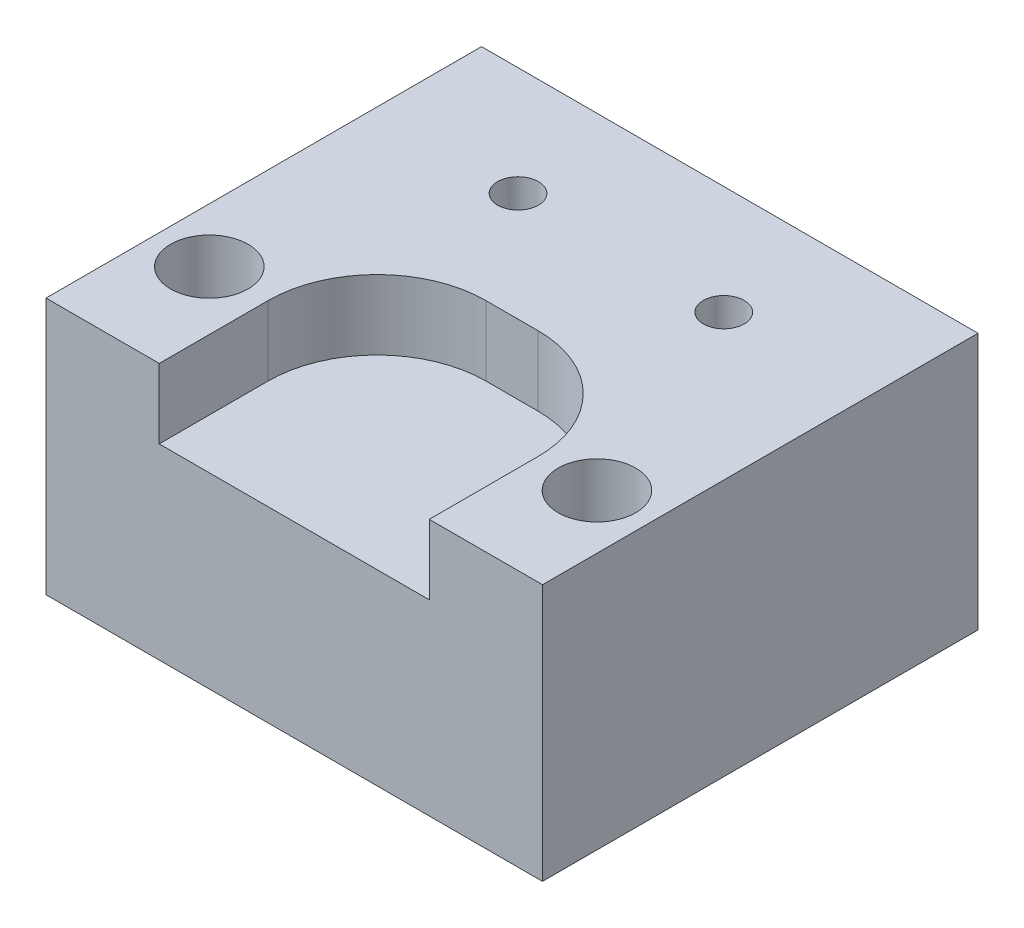
SolidWorks part; units mm, degrees
ref_plane "Front Plane" through (0, 0, 0) normal (0, 0, 1) x (1, 0, 0)
ref_plane "Top Plane" through (0, 0, 0) normal (0, 1, 0) x (1, 0, 0)
ref_plane "Right Plane" through (0, 0, 0) normal (1, 0, 0) x (0, 0, -1)
sketch "Sketch1" plane through (0, 0, 0) normal (0, 1, 0) x (1, 0, 0)
  line L1 (-7.239, -6.35) -> (7.239, -6.35)
  line L2 (-7.239, -6.35) -> (-7.239, 6.35)
  line L3 (-7.239, 6.35) -> (7.239, 6.35)
  line L4 (7.239, -6.35) -> (7.239, 6.35)
  line L5 (-7.239, -6.35) -> (7.239, 6.35) construction
  line L6 (-7.239, 6.35) -> (7.239, -6.35) construction
  point P0 (0, 0)
  dimension "D1" = 14.478
  dimension "D2" = 12.7
extrude "Boss-Extrude1" add sketch "Sketch1" along normal blind 7.493
hole_wizard "#0-80 Tapped Hole1" positions "Sketch3" profile "Sketch2" tap size "#0-80" standard "Ansi Inch" end condition through all
sketch "Sketch3" plane through (0, 7.493, 0) normal (0, 1, 0) x (-1, 0, 0)
  line L0 (-7.239, -6.35) -> (7.239, -6.35) construction
  point P0 (3, -3.175)
  point P1 (-3, -3.175)
  dimension "D1" = 3
  dimension "D2" = 3
  dimension "D3" = 3.175
sketch "Sketch2" plane through (-3, 7.493, -3.175) normal (1, 0, 0) x (0, 0, 1)
  line L0 (0, 0) -> (0, 7.493)
  line L1 (0, 7.493) -> (0.5956, 7.493)
  line L2 (0.5956, 7.493) -> (0.5956, 0)
  line L5 (0.5956, 0) -> (0, 0)
  line L11 (0, -6.35) -> (0, 107.95) construction
  dimension "Thread Major Dia." = 1.1913
  dimension "Thru Tap Drill Depth" = 7.493
hole_wizard "#2 Clearance Hole1" positions "Sketch5" profile "Sketch4" hole size "#2" standard "Ansi Inch" end condition through all
sketch "Sketch5" plane through (0, 7.493, 0) normal (0, 1, 0) x (-1, 0, 0)
  line L0 (7.239, 6.35) -> (-7.239, 6.35) construction
  line L1 (-7.239, 6.35) -> (-7.239, -6.35) construction
  line L2 (7.239, -6.35) -> (7.239, 6.35) construction
  point P0 (5.6515, 3.175)
  point P1 (-5.6515, 3.175)
  dimension "D1" = 3.175
  dimension "D2" = 1.5875
  dimension "D3" = 1.5875
sketch "Sketch4" plane through (-5.6515, 7.493, 3.175) normal (1, 0, 0) x (0, 0, 1)
  line L0 (0, 0) -> (0, 7.493)
  line L1 (0, 7.493) -> (1.1303, 7.493)
  line L2 (1.1303, 7.493) -> (1.1303, 0)
  line L5 (1.1303, 0) -> (0, 0)
  line L11 (0, -6.35) -> (0, 107.95) construction
  dimension "Thru Hole Dia." = 2.2606
  dimension "Thru Hole Depth" = 7.493
hole_wizard "3/64 (0.04688) Diameter Hole1" positions "Sketch7" profile "Sketch6" hole size "3/64" standard "Ansi Inch"
sketch "Sketch7" plane through (0, 0, -6.35) normal (0, 0, -1) x (-1, 0, 0)
  line L0 (-7.239, 7.493) -> (-7.239, 0) construction
  line L1 (7.239, 7.493) -> (7.239, 0) construction
  point P0 (-2.9972, 3.7465)
  point P1 (2.9972, 3.7465)
  point P7 (-7.239, 3.7465)
  dimension "D1" = 4.2418
  dimension "D2" = 4.2418
sketch "Sketch6" plane through (2.9972, 3.7465, -6.35) normal (1, 0, 0) x (0, 1, 0)
  line L0 (0, 0) -> (0, 5.1202)
  line L1 (0, 5.1202) -> (0.5954, 4.7625)
  line L2 (0.5954, 4.7625) -> (0.5954, 0)
  line L5 (0.5954, 0) -> (0, 0)
  line L10 (0, 5.1202) -> (-0.5954, 4.7625) construction
  line L11 (0, -6.35) -> (0, 107.95) construction
  dimension "Hole Dia." = 1.1908
  dimension "Hole Depth" = 4.7625
  dimension "Drill Angle" = 118
sketch "Sketch8" plane through (0, 7.493, 0) normal (0, -1, 0) x (1, 0, 0)
  line L0 (-7.239, 6.35) -> (7.239, 6.35) construction
  line L1 (3.937, 0) -> (-3.937, 0)
  line L2 (3.937, 0) -> (3.937, 12.7)
  line L3 (3.937, 12.7) -> (-3.937, 12.7)
  line L4 (-3.937, 0) -> (-3.937, 12.7)
  line L5 (3.937, 0) -> (-3.937, 12.7) construction
  line L6 (3.937, 12.7) -> (-3.937, 0) construction
  point P0 (0, 6.35)
  dimension "D1" = 7.874
  dimension "D2" = 12.7
extrude "Cut-Extrude1" cut sketch "Sketch8" along normal blind 2.032
fillet "Fillet1" radius 3.175 2 edges at (3.937, 6.477, 0) (-3.937, 6.477, 0)
